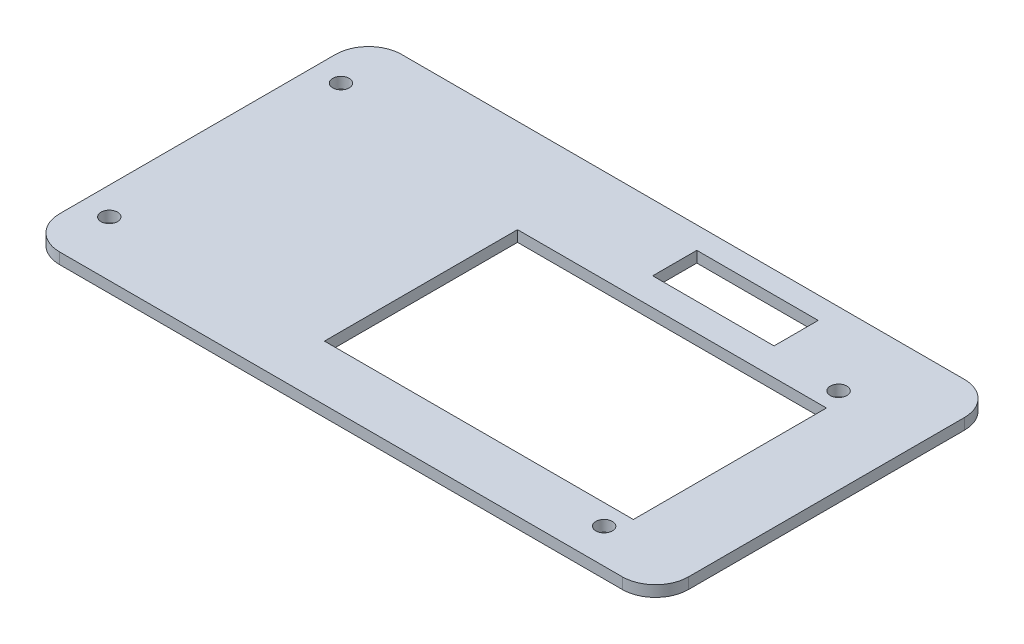
SolidWorks part; units mm, degrees
material "Плата обработки данных, простая"
ref_plane "Спереди" through (0, 0, 0) normal (0, 0, 1) x (1, 0, 0)
ref_plane "Сверху" through (0, 0, 0) normal (0, 1, 0) x (1, 0, 0)
ref_plane "Справа" through (0, 0, 0) normal (1, 0, 0) x (0, 0, -1)
sketch "Эскиз1" plane through (0, 0, 0) normal (0, 1, 0) x (1, 0, 0)
  line L0 (31.5, 0) -> (-82.5, 0) construction
  line L1 (-38.5, -21) -> (17.5, -21)
  line L2 (-38.5, -21) -> (-38.5, 14)
  line L3 (-38.5, 14) -> (17.5, 14)
  line L4 (17.5, -21) -> (17.5, 14)
  line L11 (-82.5, -31) -> (-82.5, -21)
  line L16 (31.5, 31) -> (-31.5, 31)
  line L17 (-82.5, 31) -> (-82.5, -21)
  line L18 (-82.5, -31) -> (31.5, -31)
  line L19 (31.5, 31) -> (31.5, -31)
  line L20 (-31.5, 31) -> (-82.5, 31)
  point P0 (0, 0)
  point P14 (31.5, 0)
extrude "Бобышка-Вытянуть1" add sketch "Эскиз1" along normal blind 2
sketch "Эскиз3" plane through (0, 2, 0) normal (0, -1, 0) x (1, 0, 0)
  line L0 (31.5, 0) -> (-82.5, 0) construction
  line L1 (31.5, 31) -> (31.5, -31) construction
  line L2 (-82.5, -31) -> (-82.5, 31) construction
  line L5 (3, -19) -> (3, -27)
  line L6 (3, -27) -> (-19, -27)
  line L7 (-19, -27) -> (-19, -19)
  line L8 (-19, -19) -> (3, -19)
  circle A0 centre (15.9, 24.7) radius 1.5
  circle A1 centre (15.9, -17.8) radius 1.5
  circle A2 centre (-77.5, 21) radius 1.5
  circle A3 centre (-77.5, -21) radius 1.5
  point P3 (0, 0)
extrude "Вырез-Вытянуть1" cut sketch "Эскиз3" along normal blind 10
fillet "Скругление1" radius 6 4 edges at (31.5, 1, -31) (31.5, 1, 31) (-82.5, 1, -31) (-82.5, 1, 31)
